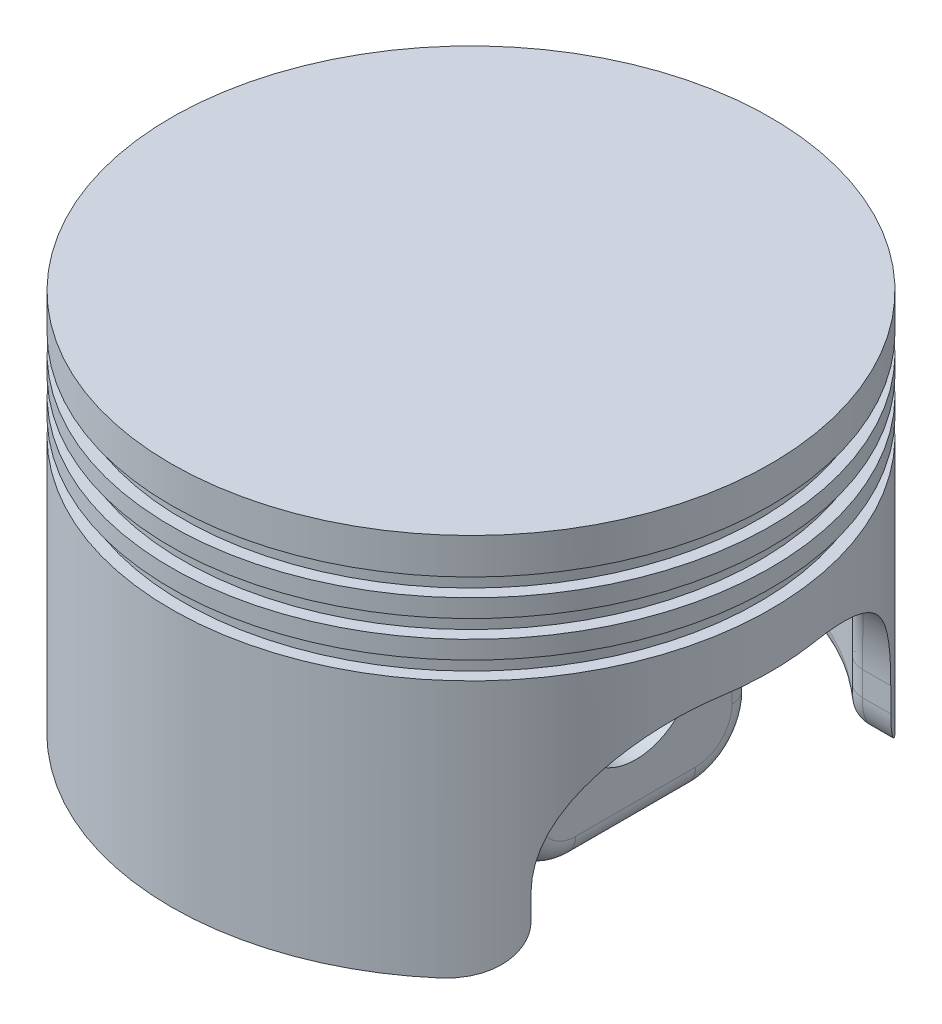
SolidWorks part; units mm, degrees
ref_plane "Front Plane" through (0, 0, 0) normal (0, 0, 1) x (1, 0, 0)
ref_plane "Top Plane" through (0, 0, 0) normal (0, 1, 0) x (1, 0, 0)
ref_plane "Right Plane" through (0, 0, 0) normal (1, 0, 0) x (0, 0, -1)
sketch "Sketch1" plane through (0, 0, 0) normal (0, 0, 1) x (1, 0, 0)
  line L1 (0, 19) -> (63.5, 19)
  line L2 (0, 19) -> (0, 0)
  line L3 (57.15, -62.28) -> (63.5, -62.28)
  line L4 (63.5, 19) -> (63.5, -62.28)
  line L5 (0, 19) -> (63.5, -62.28) construction
  line L6 (0, -62.28) -> (63.5, 19) construction
  line L9 (0, 0) -> (57.15, 0)
  line L10 (57.15, -62.28) -> (57.15, 0)
  line L11 (0, -62.28) -> (57.15, 0) construction
  line L12 (0, 0) -> (57.15, -62.28) construction
  point P0 (0, 0)
  point P9 (28.575, -31.14)
  point P10 (29.4557, -37.7033)
  point P11 (0, 0)
  point P12 (0, 0)
  point P13 (0, 0)
  point P14 (0, 0)
  dimension "D1" = 63.5
  dimension "D2" = 81.28
  dimension "D3" = 6.35
  dimension "D4" = 19
  dimension "D5" = 0
revolve "Revolve1" add sketch "Sketch1" angle 360 about L2
sketch "Sketch2" plane through (0, 0, 0) normal (0, 0, 1) x (1, 0, 0)
  line L0 (63.5, 11.38) -> (60.96, 11.38)
  line L1 (60.96, 11.38) -> (60.96, 7.57)
  line L2 (60.96, 7.57) -> (63.5, 7.57)
  line L3 (63.5, 19) -> (-63.5, 19) construction
  line L5 (63.5, 11.38) -> (63.5, 7.57)
  dimension "D1" = 7.62
  dimension "D2" = 3.81
  dimension "D3" = 2.54
  dimension "D4" = 63.5
ref_axis "Axis1" through (0, -66.344, 0) along (0, 1, 0)
revolve "Cut-Revolve1" cut sketch "Sketch2" angle 360 about axis through (0, -66.344, 0) along (0, 1, 0)
pattern_linear "LPattern1" count 3 spacing 7.62 along (0, -1, 0) of "Cut-Revolve1"
sketch "Sketch3" plane through (0, 0, 0) normal (1, 0, 0) x (0, 0, -1)
  line L0 (0, -66.344) -> (0, 23.064) construction
  line L1 (-38.1, -19.1) -> (38.1, -19.1)
  line L2 (-38.1, -19.1) -> (-38.1, -62.28)
  line L3 (-38.1, -62.28) -> (38.1, -62.28)
  line L4 (38.1, -19.1) -> (38.1, -62.28)
  line L5 (-38.1, -19.1) -> (38.1, -62.28) construction
  line L6 (-38.1, -62.28) -> (38.1, -19.1) construction
  line L7 (-57.15, -62.28) -> (57.15, -62.28) construction
  line L8 (63.5, 19) -> (-63.5, 19) construction
  point P0 (0, -40.69)
  dimension "D1" = 76.2
  dimension "D2" = 38.1
extrude "Cut-Extrude1" cut sketch "Sketch3" against normal through all both and the other way through all
fillet "Fillet1" radius 28 4 edges at (-46.6985, -19.1, 38.1) (-46.6985, -19.1, -38.1) (46.6985, -19.1, -38.1) (46.6985, -19.1, 38.1)
sketch "Sketch4" plane through (0, 0, 0) normal (0, -1, 0) x (-1, 0, 0)
  line L1 (34.88, -25.4) -> (15.88, -25.4)
  line L2 (34.88, -25.4) -> (34.88, 25.4)
  line L3 (34.88, 25.4) -> (15.88, 25.4)
  line L4 (15.88, -25.4) -> (15.88, 25.4)
  line L5 (34.88, -25.4) -> (15.88, 25.4) construction
  line L6 (34.88, 25.4) -> (15.88, -25.4) construction
  point P0 (25.38, 0)
  dimension "D1" = 19
  dimension "D2" = 15.88
  dimension "D3" = 50.8
extrude "Boss-Extrude1" add sketch "Sketch4" along normal up to surface (62.28 mm away) up to face at (0, -62.28, 49.2125)
mirror "Mirror1" about plane through (0, 0, 0) normal (1, 0, 0) of "Boss-Extrude1"
sketch "Sketch5" plane through (-34.88, 0, 0) normal (-1, 0, 0) x (0, 0, 1)
  line L0 (0, -66.344) -> (0, 23.064) construction
  line L1 (-25.4, -62.28) -> (25.4, -62.28) construction
  circle A0 centre (0, -36.88) radius 12.7
  dimension "D2" = 25.4
  dimension "D1" = 25.4
extrude "Cut-Extrude2" cut sketch "Sketch5" against normal up to surface (69.76 mm away) and the other way through all up to face at (34.88, -31.14, 0)
fillet "Fillet2" radius 12.7 4 edges at (25.38, -62.28, 25.4) (25.38, -62.28, -25.4) (-25.38, -62.28, 25.4) (-25.38, -62.28, -25.4)
fillet "Fillet3" radius 10 4 edges at (-46.6985, -62.28, -38.1) (-46.6985, -62.28, 38.1) (46.6985, -62.28, -38.1) (46.6985, -62.28, 38.1)
fillet "Fillet4" radius 5 20 edges at (-34.88, -24.79, -25.4) (-34.88, -58.5603, -21.6803) (-34.88, -24.79, 25.4) (-34.88, -58.5603, 21.6803) (-15.88, -24.79, 25.4) (-15.88, -58.5603, 21.6803) (-15.88, -24.79, -25.4) (-15.88, -58.5603, -21.6803) (34.88, -24.79, -25.4) (34.88, -58.5603, -21.6803) (34.88, -24.79, 25.4) (34.88, -58.5603, 21.6803) (15.88, -24.79, 25.4) (15.88, -58.5603, 21.6803) (15.88, -24.79, -25.4) (15.88, -58.5603, -21.6803) (-34.88, -62.28, 0) (-15.88, -62.28, 0) (34.88, -62.28, 0) (15.88, -62.28, 0)
fillet "Fillet5" radius 5 16 edges at (17.3445, 0, -23.9355) (25.38, 0, -25.4) (33.4155, 0, -23.9355) (34.88, 0, 0) (33.4155, 0, 23.9355) (25.38, 0, 25.4) (17.3445, 0, 23.9355) (-33.4155, 0, 23.9355) (-25.38, 0, 25.4) (-17.3445, 0, 23.9355) (-15.88, 0, 0) (-17.3445, 0, -23.9355) (-25.38, 0, -25.4) (-33.4155, 0, -23.9355) (15.88, 0, 0) (-34.88, 0, 0)
fillet "Fillet6" radius 5 16 edges at (40.0022, -59.1316, -40.816) (42.5971, -49.69, -38.1) (46.055, -32.2516, -33.8387) (57.15, -19.1, 0) (50.4318, -24.6881, 26.8841) (42.5971, -49.69, 38.1) (41.3657, -57.2692, 39.4335) (0, -62.28, 57.15) (-40.0022, -59.1316, 40.816) (-42.5971, -49.69, 38.1) (-46.055, -32.2516, 33.8387) (-57.15, -19.1, 0) (-50.4318, -24.6881, -26.8841) (-42.5971, -49.69, -38.1) (-41.3657, -57.2692, -39.4335) (0, -62.28, -57.15)
